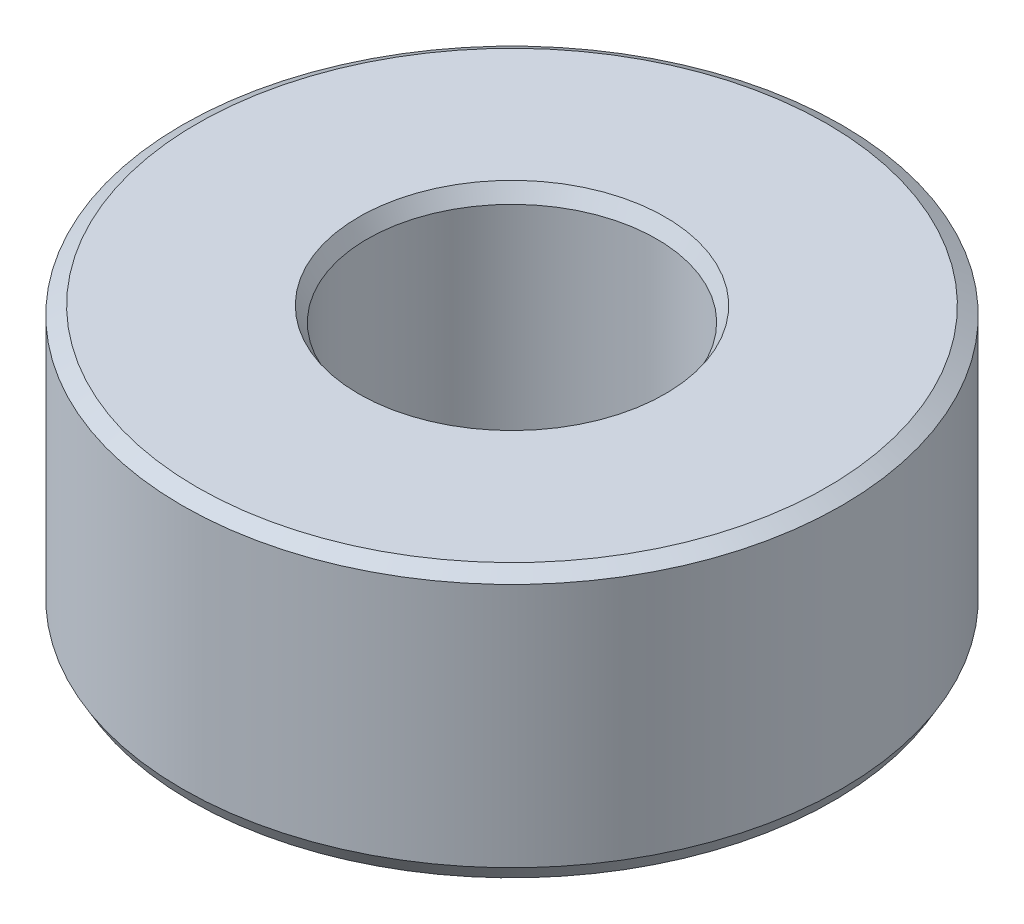
SolidWorks part; units mm, degrees
ref_plane "Front Plane" through (0, 0, 0) normal (0, 0, 1) x (1, 0, 0)
ref_plane "Top Plane" through (0, 0, 0) normal (0, 1, 0) x (1, 0, 0)
ref_plane "Right Plane" through (0, 0, 0) normal (1, 0, 0) x (0, 0, -1)
sketch "Sketch1" plane through (0, 0, 0) normal (0, 1, 0) x (1, 0, 0)
  circle A0 centre (0, 0) radius 37.5
  dimension "SLEEVE_OD" = 75
extrude "Boss-Extrude1" add sketch "Sketch1" along normal blind 30.5505
sketch "Sketch2" plane through (0, 0, 0) normal (0, 1, 0) x (1, 0, 0)
  circle A0 centre (0, 0) radius 16.462
  dimension "BORE_D" = 32.9239
extrude "Cut-Extrude1" cut sketch "Sketch2" along normal through all
chamfer "Chamfer1" distance 0.9693 angle 60 4 edges at (0, 30.5505, 16.462) (0, 0, 16.462) (0, 0, 37.5) (0, 30.5505, 37.5) first distance on face at (0, 30.5505, 16.462) first distance on face at (0, 0, 16.462) first distance on face at (0, 30.5505, 37.5)
